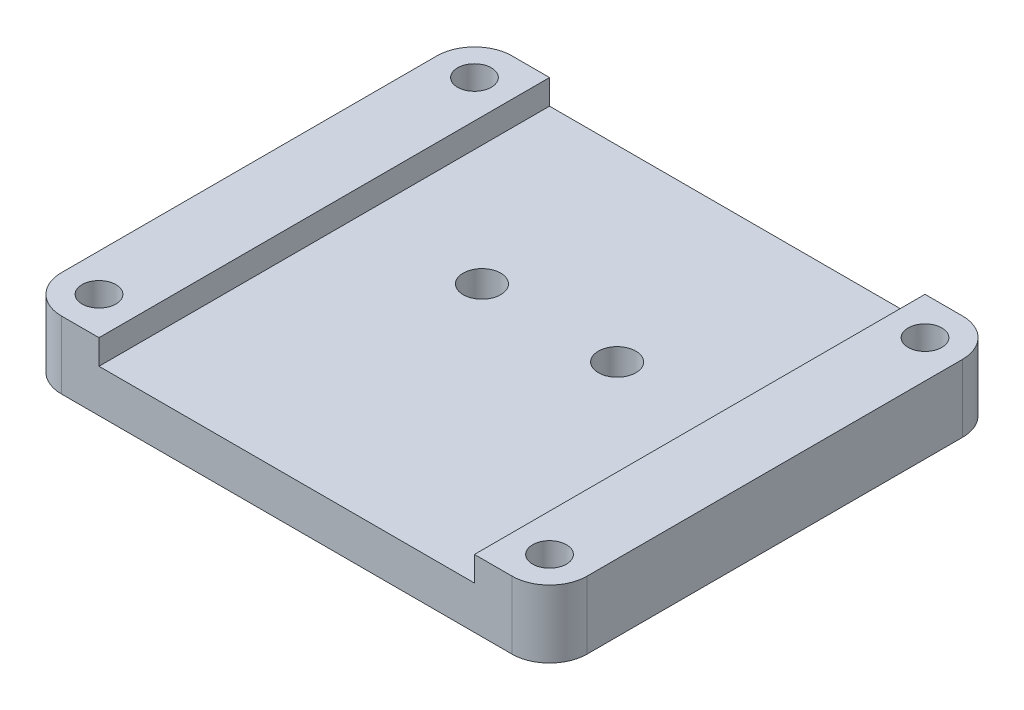
SolidWorks part; units mm, degrees
ref_plane "Front Plane" through (0, 0, 0) normal (0, 0, 1) x (1, 0, 0)
ref_plane "Top Plane" through (0, 0, 0) normal (0, 1, 0) x (1, 0, 0)
ref_plane "Right Plane" through (0, 0, 0) normal (1, 0, 0) x (0, 0, -1)
sketch "Sketch1" plane through (0, 0, 0) normal (0, 1, 0) x (1, 0, 0)
  line L1 (-35, 30) -> (35, 30)
  line L2 (-35, 30) -> (-35, -30)
  line L3 (-35, -30) -> (35, -30)
  line L4 (35, 30) -> (35, -30)
  dimension "D1" = 70
  dimension "D2" = 35
  dimension "D3" = 60
  dimension "D4" = 30
extrude "Boss-Extrude1" add sketch "Sketch1" along normal blind 5.7 contours L2 L3 L4 L1
sketch "Sketch2" plane through (0, 5.7, 0) normal (0, 1, 0) x (1, 0, 0)
  line L0 (-8.6368, 0) -> (9.5563, 0) construction
  line L1 (0, 10.6401) -> (0, -12.9388) construction
  line L2 (-35, 30) -> (-35, -30) construction
  line L3 (-35, 30) -> (35, 30) construction
  line L4 (-35, -30) -> (35, -30) construction
  line L5 (-35, 30) -> (-25, 30)
  line L6 (-35, 30) -> (-35, -30)
  line L7 (-35, -30) -> (-25, -30)
  line L8 (-25, 30) -> (-25, -30)
  line L10 (35, 30) -> (25, 30)
  line L11 (35, 30) -> (35, -30)
  line L12 (35, -30) -> (25, -30)
  line L13 (25, 30) -> (25, -30)
  circle A0 centre (-30, 25) radius 2.25
  circle A1 centre (-30, -25) radius 2.25
  circle A2 centre (30, -25) radius 2.25
  circle A3 centre (30, 25) radius 2.25
  circle A4 centre (-9, 5) radius 2.5
  circle A5 centre (9, 5) radius 2.5
  line M5 (35, 30) -> (-35, 30)
  line M6 (-35, 30) -> (-35, -30)
  line M7 (-35, -30) -> (35, -30)
  line M8 (35, -30) -> (35, 30)
  dimension "D1" = 4.5
  dimension "D6" = 5
  dimension "D7" = 9
  dimension "D2" = 5
  dimension "D3" = 5
  dimension "D4" = 10
  dimension "D5" = 10
  dimension "D8" = 5
extrude "Boss-Extrude2" add sketch "Sketch2" along normal blind 3.3 contours L8 A0 A1 M5 M6 M7 | L13 A2 A3 M5 M7 M8 region at (-30, 5.7, 0) region at (30, 5.7, 0)
fillet "Fillet1" radius 5 4 edges at (35, 4.5, 30) (35, 4.5, -30) (-35, 4.5, -30) (-35, 4.5, 30)
extrude "Cut-Extrude2" cut sketch "Sketch2<4>" against normal blind 5 contours A4 | A5 region at (-9, 5.7, -5) region at (9, 5.7, -5)
sketch "Sketch2<4>" plane through (0, 5.7, 0) normal (0, 1, 0) x (1, 0, 0) same geometry as "Sketch2"
